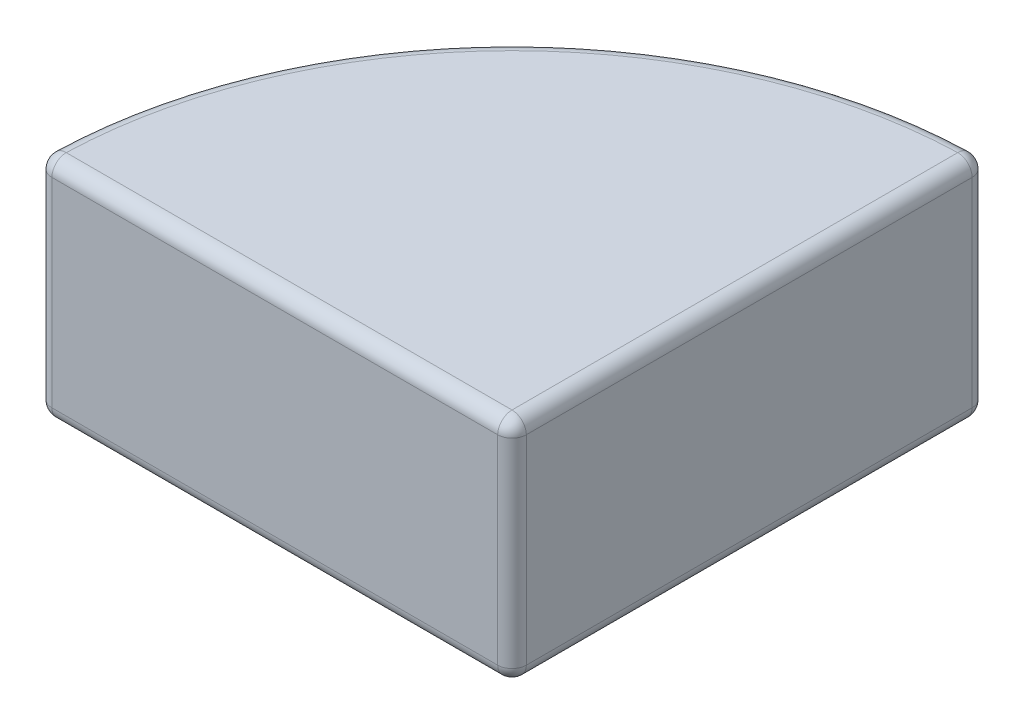
SolidWorks part; units mm, degrees
ref_plane "Front Plane" through (0, 0, 0) normal (0, 0, 1) x (1, 0, 0)
ref_plane "Top Plane" through (0, 0, 0) normal (0, 1, 0) x (1, 0, 0)
ref_plane "Right Plane" through (0, 0, 0) normal (1, 0, 0) x (0, 0, -1)
sketch "Sketch1" plane through (0, 0, 0) normal (0, 1, 0) x (1, 0, 0)
  line L0 (0, 0) -> (-331.6, 0)
  line L1 (0, 0) -> (0, 331.6)
  arc A0 (-331.6, 0) -> (0, 331.6) centre (0, 0) cw
  dimension "D1" = 331.6
extrude "Boss-Extrude1" add sketch "Sketch1" along normal blind 159.4
shell "Shell1" thickness 20 removed face at (-133.4255, 0, -133.4255)
fillet "Fillet1" radius 10 18 edges at (-234.4766, 0, -234.4766) (0, 79.7, -331.6) (0, 0, -165.8) (-234.4766, 159.4, -234.4766) (0, 159.4, -165.8) (-331.6, 79.7, 0) (-165.8, 159.4, 0) (0, 79.7, 0) (-165.8, 0, 0) (-220.3345, 0, -220.3345) (-20, 0, -165.4787) (-165.4787, 0, -20) (-20, 69.7, -20) (-310.9575, 69.7, -20) (-20, 69.7, -310.9575) (-220.3345, 139.4, -220.3345) (-165.4787, 139.4, -20) (-20, 139.4, -165.4787)
